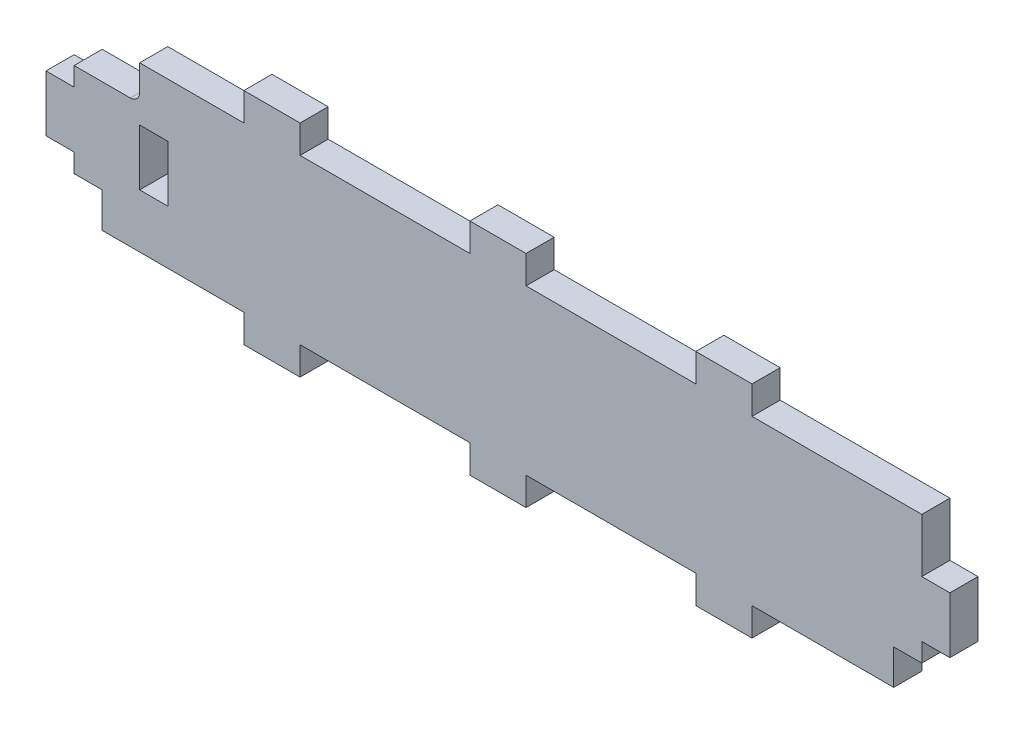
SolidWorks part; units mm, degrees
ref_plane "Front Plane" through (0, 0, 0) normal (0, 0, 1) x (1, 0, 0)
ref_plane "Top Plane" through (0, 0, 0) normal (0, 1, 0) x (1, 0, 0)
ref_plane "Right Plane" through (0, 0, 0) normal (1, 0, 0) x (0, 0, -1)
sketch "Sketch2" plane through (0, 0, 0) normal (0, 1, 0) x (1, 0, 0)
  line L0 (0, 0) -> (0, 6) construction
  dimension "D1" = 6
sketch "Sketch1" plane through (0, 0, 0) normal (0, 0, 1) x (1, 0, 0)
  line L1 (-96.5, -23.5) -> (96.5, -23.5)
  line L2 (-96.5, -23.5) -> (-96.5, 23.5)
  line L3 (-96.5, 23.5) -> (96.5, 23.5)
  line L4 (96.5, -23.5) -> (96.5, 23.5)
  line L5 (-96.5, -23.5) -> (96.5, 23.5) construction
  line L6 (-96.5, 23.5) -> (96.5, -23.5) construction
  point P0 (0, 0)
  dimension "D1" = 193
  dimension "D2" = 47
extrude "Boss-Extrude1" add sketch "Sketch1" against normal up to vertex (6 mm away) contours L2 L3 L4 L1 up to point (0, 0, -6)
sketch "Sketch3" plane through (0, 0, 0) normal (0, 0, 1) x (1, 0, 0)
  line L0 (-96.5, -23.5) -> (96.5, -23.5) construction
  line L1 (-96.5, 23.5) -> (-90.5, 23.5)
  line L2 (-96.5, 23.5) -> (-96.5, -23.5)
  line L3 (-96.5, -23.5) -> (-90.5, -23.5)
  line L4 (-90.5, 23.5) -> (-90.5, -23.5)
  line L5 (-76.5, 23.5) -> (-76.5, -23.5) construction
  line L6 (96.5, 23.5) -> (90.5, 23.5)
  line L7 (96.5, 23.5) -> (96.5, -23.5)
  line L8 (96.5, -23.5) -> (90.5, -23.5)
  line L9 (90.5, 23.5) -> (90.5, -23.5)
  line L10 (-90.5, 10) -> (90.5, 10) construction
  line L11 (-90.5, 10) -> (-90.5, -10) construction
  line L12 (-90.5, -10) -> (90.5, -10) construction
  line L13 (90.5, 10) -> (90.5, -10) construction
  line L14 (0, -10) -> (0, 10) construction
  line L15 (-96.5, 23.5) -> (96.5, 23.5) construction
  line L16 (-76.5, 23.5) -> (-70.5, 23.5) construction
  line L17 (-70.5, 23.5) -> (-70.5, -23.5) construction
  line L18 (-70.5, -23.5) -> (-76.5, -23.5) construction
  line L19 (-90.5, 0) -> (-96.5, 0) construction
  line L20 (-90.5, 6) -> (-96.5, 6)
  line L21 (-90.5, 6) -> (-90.5, -6)
  line L22 (-90.5, -6) -> (-96.5, -6)
  line L23 (-96.5, 6) -> (-96.5, -6)
  line L24 (-84.5, -10) -> (-84.5, -17.5)
  line L25 (-84.5, -17.5) -> (-90.5, -17.5)
  line L26 (-84.5, -17.5) -> (-84.5, -23.5)
  line L27 (-76.5, 23.5) -> (-76.5, 17.5) construction
  line L28 (-76.5, 17.5) -> (-90.5, 17.5) construction
  line L29 (-84.5, -17.5) -> (-76.5, -17.5) construction
  line L33 (-84.5, -10) -> (-90.5, -10)
  line M26 (-96.5, -23.5) -> (96.5, -23.5)
  line M28 (96.5, 23.5) -> (-96.5, 23.5)
  line M29 (-96.5, 23.5) -> (-96.5, -23.5)
  dimension "D1" = 6
  dimension "D2" = 20
  dimension "D3" = 14
  dimension "D4" = 12
  dimension "D5" = 6
  dimension "D6" = 7.5
  dimension "D7" = 8
extrude "Cut-Extrude1" cut sketch "Sketch3" against normal through all contours L20 L4 M28 M29 | L4 L22 M29 M26 | L24 L33 L4 L25 region at (-93.5, 14.75, 0) region at (-93.5, -14.75, 0) region at (-87.5, -13.75, 0)
mirror "Mirror1" about plane through (0, 0, 0) normal (1, 0, 0) of "Cut-Extrude1"
sketch "Sketch4" plane through (0, 0, 0) normal (0, 0, 1) x (1, 0, 0)
  line L0 (-96.5, -23.5) -> (96.5, -23.5) construction
  line L1 (-6, -17.5) -> (6, -17.5) construction
  line L2 (-6, -17.5) -> (-6, -23.5) construction
  line L3 (-6, -23.5) -> (6, -23.5) construction
  line L4 (6, -17.5) -> (6, -23.5) construction
  line L5 (-90.5, -17.5) -> (-54.25, -17.5) construction
  line L6 (42.25, -17.5) -> (54.25, -17.5) construction
  line L7 (42.25, -17.5) -> (42.25, -23.5) construction
  line L8 (42.25, -23.5) -> (54.25, -23.5) construction
  line L9 (54.25, -17.5) -> (54.25, -23.5) construction
  line L10 (-42.25, -17.5) -> (-54.25, -17.5) construction
  line L11 (-42.25, -17.5) -> (-42.25, -23.5) construction
  line L12 (-42.25, -23.5) -> (-54.25, -23.5) construction
  line L13 (-54.25, -17.5) -> (-54.25, -23.5) construction
  line L14 (-42.25, -17.5) -> (-6, -17.5) construction
  line L15 (42.25, -17.5) -> (6, -17.5) construction
  line L16 (54.25, -17.5) -> (90.5, -17.5) construction
  line L19 (-90.5, -17.5) -> (-54.25, -17.5)
  line L20 (-90.5, -17.5) -> (-90.5, -23.5)
  line L21 (-90.5, -23.5) -> (-54.25, -23.5)
  line L22 (-54.25, -17.5) -> (-54.25, -23.5)
  line L23 (-42.25, -23.5) -> (-6, -23.5)
  line L24 (-42.25, -23.5) -> (-42.25, -17.5)
  line L25 (-42.25, -17.5) -> (-6, -17.5)
  line L26 (-6, -23.5) -> (-6, -17.5)
  line L27 (6, -17.5) -> (42.25, -17.5)
  line L28 (6, -17.5) -> (6, -23.5)
  line L29 (6, -23.5) -> (42.25, -23.5)
  line L30 (42.25, -17.5) -> (42.25, -23.5)
  line L31 (54.25, -23.5) -> (90.5, -23.5)
  line L32 (54.25, -23.5) -> (54.25, -17.5)
  line L33 (54.25, -17.5) -> (90.5, -17.5)
  line L34 (90.5, -23.5) -> (90.5, -17.5)
  line M36 (-84.5, -17.5) -> (-90.5, -17.5)
  line M37 (-90.5, -17.5) -> (-90.5, -23.5)
  line M38 (-90.5, -23.5) -> (90.5, -23.5)
  line M39 (90.5, -23.5) -> (90.5, -17.5)
  line M40 (90.5, -17.5) -> (84.5, -17.5)
  dimension "D1" = 12
extrude "Cut-Extrude2" cut sketch "Sketch4" against normal through all contours L22 L19 M36 M37 M38 | L26 L25 L24 M38 | L30 L27 L28 M38 | L33 L32 M38 M39 M40 region at (72.375, -20.5, 0) region at (24.125, -20.5, 0) region at (-24.125, -20.5, 0) region at (-72.375, -20.5, 0)
mirror "Mirror2" about plane through (0, 0, 0) normal (0, 1, 0) of "Cut-Extrude2"
sketch "Sketch5" plane through (0, 0, 0) normal (0, 0, 1) x (1, 0, 0)
  line L0 (-76.5, 23.5) -> (-76.5, -23.5) construction
  line L1 (-76.5, 17.5) -> (-90.5, 17.5)
  line L2 (-76.5, 17.5) -> (-76.5, 10)
  line L3 (-76.5, 10) -> (-90.5, 10)
  line L4 (-90.5, 17.5) -> (-90.5, 10)
  line L5 (-76.5, 6) -> (-70.5, 6)
  line L6 (-76.5, 6) -> (-76.5, -6)
  line L7 (-76.5, -6) -> (-70.5, -6)
  line L8 (-70.5, 6) -> (-70.5, -6)
  line L9 (-70.5, 23.5) -> (-70.5, -23.5) construction
  line L10 (-90.5, 6) -> (-96.5, 6) construction
  line L11 (-90.5, -6) -> (-96.5, -6) construction
extrude "Cut-Extrude3" cut sketch "Sketch5" against normal through all
fillet "Fillet1" radius 2 1 edges at (-76.5, 10, -3)
equation "\"t_wood\"= 6' Thickness of the wood"
equation "\"t_glass\"= 2.5'Thickness of glass panels"
equation "\"w_glass\"= 181"
equation "\"h_glass\"= 151"
equation "\"h_food_internal\" = 60"
equation "\"entry_height\"= 20"
equation "\"entry diameter\"= 8"
equation "\"glass_bottom_overlap\"= 8"
equation "\"default_finger_size\"= 12"
equation "\"brood_depth\"= 42"
equation "\"outer_box_depth\" = \"brood_depth\" + ( 2 * \"t_glass\" ) + ( 2 * \"t_wood\" )"
equation "\"outer_box_width\"= \"w_glass\" + ( 2 * \"t_wood\" )"
equation "\"food_top_clearance\"= 10"
equation "\"outer_box_height\"= \"t_wood\" + \"h_glass\" + \"t_wood\" + \"h_food_internal\" + \"food_top_clearance\" + \"t_wood\""
equation "\"food_internal_depth\"= \"brood_depth\" + \"t_glass\" + \"t_glass\" - \"t_wood\" - \"t_wood\""
equation "\"food_channel_clearance_width\"= 14"
equation "\"bar_top_play\"= 0.5"
equation "\"bar_entry_angle\"= 10"
equation "\"bar_width\"= 20"
equation "\"entry_disk_play\"= 0.3"
equation "\"D1@Sketch2\"=\"t_wood\""
equation "\"D1@Sketch1\"=\"outer_box_width\""
equation "\"D2@Sketch1\"=\"brood_depth\"+\"t_glass\"+\"t_glass\""
equation "\"D1@Sketch3\"=\"t_wood\""
equation "\"D2@Sketch3\"=\"bar_width\""
equation "\"D3@Sketch3\"=\"food_channel_clearance_width\""
equation "\"D4@Sketch3\"=\"default_finger_size\""
equation "\"D5@Sketch3\"=\"t_wood\""
equation "\"D1@Sketch4\"=\"default_finger_size\""
